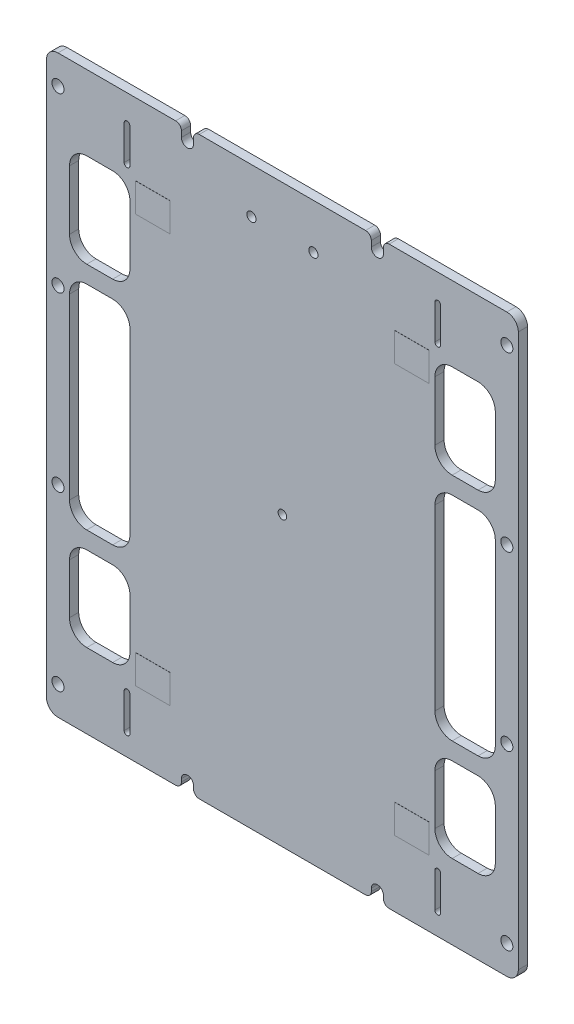
SolidWorks part; units mm, degrees
material "FR4_stuffedProtoboard"
ref_plane "Front Plane" through (0, 0, 0) normal (0, 0, 1) x (1, 0, 0)
ref_plane "Top Plane" through (0, 0, 0) normal (0, 1, 0) x (1, 0, 0)
ref_plane "Right Plane" through (0, 0, 0) normal (1, 0, 0) x (0, 0, -1)
sketch "Sketch1" plane through (0, 0, 0) normal (0, 0, 1) x (1, 0, 0)
  line L1 (-39, -50) -> (39, -50)
  line L2 (-41, -48) -> (-41, 48)
  line L3 (-39, 50) -> (39, 50)
  line L4 (41, -48) -> (41, 48)
  line L5 (-41, -50) -> (41, 50) construction
  line L6 (-41, 50) -> (41, -50) construction
  arc A0 (-39, -50) -> (-41, -48) centre (-39, -48) cw
  arc A1 (39, -50) -> (41, -48) centre (39, -48) ccw
  arc A2 (39, 50) -> (41, 48) centre (39, 48) cw
  arc A3 (-41, 48) -> (-39, 50) centre (-39, 48) cw
  point P0 (0, 0)
  dimension "D3" = 2
  dimension "D1" = 100
  dimension "D2" = 82
extrude "boardOutline" add sketch "Sketch1" along normal blind 1.6
sketch "Sketch2" plane through (0, 0, 1.6) normal (0, 0, 1) x (1, 0, 0)
  line L0 (39, 50) -> (-39, 50) construction
  line L1 (-41, 48) -> (-41, -48) construction
  line L3 (-37.5, 44.2) -> (-37.5, 4.2) construction
  circle A0 centre (0, 0) radius 0.75
  circle A1 centre (-37.5, 44.2) radius 1.05 construction
  circle A2 centre (37.5, 44.2) radius 1.05 construction
  circle A3 centre (37.5, 4.2) radius 1.05 construction
  circle A4 centre (37.5, -35.8) radius 1.05 construction
  circle A5 centre (-37.5, 4.2) radius 1.05 construction
  circle A6 centre (-37.5, -35.8) radius 1.05 construction
  circle A7 centre (-5.38, 42.15) radius 0.8
  circle A8 centre (5.39, 42.15) radius 0.8
  dimension "D1" = 1.5
  dimension "D2" = 2.1
  dimension "D9" = 10.77
  dimension "D7" = 1.6
  dimension "D11" = 7.85
  dimension "D12" = 35.62
  dimension "D3" = 5.8
  dimension "D4" = 3.5
  dimension "D8" = 40
  dimension "D10" = 37.5
  dimension "D5" = 2
  dimension "D6" = 3
extrude "componentHoles" cut sketch "Sketch2" against normal through all
sketch "Sketch4" plane through (0, 0, 1.6) normal (0, 0, 1) x (1, 0, 0)
  line L0 (-27, 39.25) -> (-27, 45.25) construction
  line L1 (-27.5, 39.25) -> (-27.5, 45.25)
  line L2 (-26.5, 39.25) -> (-26.5, 45.25)
  line L3 (39, 50) -> (-39, 50) construction
  line L4 (-41, 48) -> (-41, -48) construction
  line L5 (27, 39.25) -> (27, 45.25) construction
  line L6 (26.5, 39.25) -> (26.5, 45.25)
  line L7 (27.5, 39.25) -> (27.5, 45.25)
  line L8 (27, -46.25) -> (27, -40.25) construction
  line L9 (26.5, -46.25) -> (26.5, -40.25)
  line L10 (27.5, -46.25) -> (27.5, -40.25)
  line L11 (-27, -46.25) -> (-27, -40.25) construction
  line L12 (-27.5, -46.25) -> (-27.5, -40.25)
  line L13 (-26.5, -46.25) -> (-26.5, -40.25)
  line L14 (-27, 39.25) -> (27, 39.25) construction
  arc A0 (-27.5, 39.25) -> (-26.5, 39.25) centre (-27, 39.25) ccw
  arc A1 (-26.5, 45.25) -> (-27.5, 45.25) centre (-27, 45.25) ccw
  arc A2 (26.5, 39.25) -> (27.5, 39.25) centre (27, 39.25) ccw
  arc A3 (27.5, 45.25) -> (26.5, 45.25) centre (27, 45.25) ccw
  arc A4 (26.5, -46.25) -> (27.5, -46.25) centre (27, -46.25) ccw
  arc A5 (27.5, -40.25) -> (26.5, -40.25) centre (27, -40.25) ccw
  arc A6 (-27.5, -46.25) -> (-26.5, -46.25) centre (-27, -46.25) ccw
  arc A7 (-26.5, -40.25) -> (-27.5, -40.25) centre (-27, -40.25) ccw
  point P2 (-27, 42.25)
  point P11 (0, 0)
  point P16 (27, 42.25)
  point P23 (27, -43.25)
  point P30 (-27, -43.25)
  dimension "D1" = 4.75
  dimension "D2" = 13.5
  dimension "D3" = 1
  dimension "D4" = 6
  dimension "D7" = 54
  dimension "D8" = 14
  dimension "D9" = 79.5
  dimension "D5" = 2
  dimension "D6" = 2
extrude "solarCellContactHoles" cut sketch "Sketch4" against normal blind 1.6
sketch "Sketch3" plane through (0, 0, 1.6) normal (0, 0, 1) x (1, 0, 0)
  line L1 (-34, 37) -> (-29.5, 37)
  line L2 (-37, 34) -> (-37, 23.7)
  line L3 (-34, 20.7) -> (-29.5, 20.7)
  line L4 (-26.5, 34) -> (-26.5, 23.7)
  line L5 (-41, 48) -> (-41, -48) construction
  line L6 (-29.5, -22.3) -> (-34, -22.3)
  line L9 (0, 50) -> (0, -50) construction
  line L10 (39, 50) -> (-39, 50) construction
  line L11 (-39, -50) -> (39, -50) construction
  line L12 (-26.5, -25.3) -> (-26.5, -34)
  line L13 (-29.5, -37) -> (-34, -37)
  line L14 (-37, -25.3) -> (-37, -34)
  line L19 (-29.5, -19.3) -> (-34, -19.3)
  line L25 (-26.5, -16.3) -> (-26.5, 14.7)
  line L26 (-29.5, 17.7) -> (-34, 17.7)
  line L27 (-37, -16.3) -> (-37, 14.7)
  arc A0 (-37, 23.7) -> (-34, 20.7) centre (-34, 23.7) ccw
  arc A1 (-29.5, 20.7) -> (-26.5, 23.7) centre (-29.5, 23.7) ccw
  arc A2 (-29.5, 37) -> (-26.5, 34) centre (-29.5, 34) cw
  arc A3 (-34, 37) -> (-37, 34) centre (-34, 34) ccw
  arc A4 (-29.5, -19.3) -> (-26.5, -16.3) centre (-29.5, -16.3) ccw
  arc A5 (-26.5, -34) -> (-29.5, -37) centre (-29.5, -34) cw
  arc A6 (-34, -37) -> (-37, -34) centre (-34, -34) cw
  arc A7 (-34, -22.3) -> (-37, -25.3) centre (-34, -25.3) ccw
  arc A8 (-29.5, -22.3) -> (-26.5, -25.3) centre (-29.5, -25.3) cw
  arc A17 (-34, -19.3) -> (-37, -16.3) centre (-34, -16.3) cw
  arc A18 (-34, 17.7) -> (-37, 14.7) centre (-34, 14.7) ccw
  arc A19 (-26.5, 14.7) -> (-29.5, 17.7) centre (-29.5, 14.7) ccw
  point P12 (-26.5, 20.7)
  point P15 (-26.5, 37)
  point P18 (-37, 37)
  dimension "D5" = 3
  dimension "D10" = 13
  dimension "D7" = 3
  dimension "D11" = 3
  dimension "D1" = 10.5
  dimension "D2" = 29.3
  dimension "D3" = 13
  dimension "D4" = 4
  dimension "D8" = 3
  dimension "D9" = 3
  dimension "D6" = 37
extrude "windows_1side" cut sketch "Sketch3" against normal through all
sketch "Sketch5" plane through (0, 0, 1.6) normal (0, 0, 1) x (1, 0, 0)
  line L0 (-41, 48) -> (-41, -48) construction
  line L1 (-25.5, 37.5) -> (-19.5, 37.5)
  line L2 (-25.5, 37.5) -> (-25.5, 32.5)
  line L3 (-25.5, 32.5) -> (-19.5, 32.5)
  line L4 (-19.5, 37.5) -> (-19.5, 32.5)
  line L6 (19.5, 37.5) -> (19.5, 32.5)
  line L7 (25.5, 37.5) -> (25.5, 32.5)
  line L8 (19.5, 32.5) -> (25.5, 32.5)
  line L9 (19.5, 37.5) -> (25.5, 37.5)
  line L10 (19.5, -33.5) -> (19.5, -38.5)
  line L11 (25.5, -33.5) -> (25.5, -38.5)
  line L12 (19.5, -38.5) -> (25.5, -38.5)
  line L13 (19.5, -33.5) -> (25.5, -33.5)
  line L14 (-25.5, -33.5) -> (-25.5, -38.5)
  line L15 (-19.5, -33.5) -> (-19.5, -38.5)
  line L16 (-25.5, -38.5) -> (-19.5, -38.5)
  line L17 (-25.5, -33.5) -> (-19.5, -33.5)
  line L18 (-25.5, 37.5) -> (19.5, 37.5) construction
  line L19 (-25.5, 37.5) -> (-25.5, -33.5) construction
  arc A0 (-27.5, 39.25) -> (-26.5, 39.25) centre (-27, 39.25) ccw construction
  dimension "D1" = 5
  dimension "D2" = 6
  dimension "D3" = 15.5
  dimension "D4" = 1.75
  dimension "D7" = 45
  dimension "D8" = 71
  dimension "D5" = 2
  dimension "D6" = 2
extrude "contactPads" add sketch "Sketch5" along normal blind 0.02
hole_wizard "M2 Clearance Hole1" positions "Sketch6" profile "Sketch7" hole size "M2" standard "ANSI Metric" end condition through all
sketch "Sketch6" plane through (0, 0, 0) normal (0, 0, -1) x (-1, 0, 0)
  line L5 (39, -50) -> (39, -45) construction
  line L6 (39, -50) -> (-39, -50) construction
  line L7 (39, -45) -> (39, -15) construction
  line L8 (39, -15) -> (39, 15) construction
  line L9 (39, 15) -> (39, 45) construction
  line L10 (39, 45) -> (39, 50) construction
  line L11 (-39, 50) -> (39, 50) construction
  line L15 (37, -27.0602) -> (41, -27.0602) construction
  line L16 (37, -25.3) -> (37, -34) construction
  line L17 (41, 48) -> (41, -48) construction
  point P0 (39, 45)
  point P27 (39, -15)
  point P36 (39, -45)
  point P38 (39, 15)
  point P73 (39, -27.0602)
  dimension "D2" = 5
sketch "Sketch7" plane through (-39, 45, 0) normal (1, 0, 0) x (0, 1, 0)
  line L0 (0, 0) -> (0, 1.62)
  line L1 (0, 1.62) -> (1.05, 1.62)
  line L2 (1.05, 1.62) -> (1.05, 0)
  line L5 (1.05, 0) -> (0, 0)
  line L11 (0, -6.35) -> (0, 107.95) construction
  dimension "Thru Hole Dia." = 2.1
  dimension "Thru Hole Depth" = 1.62
sketch "Sketch10" plane through (0, 0, 0) normal (0, 0, -1) x (-1, 0, 0)
  line L0 (16.5, 48) -> (16.5, 55.0732) construction
  line L1 (15.45, 48) -> (15.45, 55.0732)
  line L2 (17.55, 48) -> (17.55, 55.0732)
  line L3 (16.5, -48.5) -> (16.5, -55.5732) construction
  line L4 (17.55, -48.5) -> (17.55, -55.5732)
  line L5 (15.45, -48.5) -> (15.45, -55.5732)
  line L6 (41, 48) -> (41, -48) construction
  line L8 (39, -50) -> (-39, -50) construction
  line L9 (-39, 50) -> (39, 50) construction
  arc A0 (15.45, 48) -> (17.55, 48) centre (16.5, 48) ccw
  arc A1 (17.55, 55.0732) -> (15.45, 55.0732) centre (16.5, 55.0732) ccw
  arc A2 (17.55, -48.5) -> (15.45, -48.5) centre (16.5, -48.5) ccw
  arc A3 (15.45, -55.5732) -> (17.55, -55.5732) centre (16.5, -55.5732) ccw
  point P2 (16.5, 51.5366)
  point P7 (16.5, -52.0366)
  dimension "D1" = 1.05
  dimension "D2" = 24.5
  dimension "D3" = 2
  dimension "D4" = 1.5
extrude "Cut-Extrude1" cut sketch "Sketch10" against normal through all both and the other way through all
fillet "Fillet3" radius 1 4 edges at (-17.55, 50, 0.8) (-15.45, 50, 0.8) (-15.45, -50, 0.8) (-17.55, -50, 0.8)
mirror "Mirror1" about plane through (0, 0, 0) normal (1, 0, 0) of "Cut-Extrude1", "Fillet3", "windows_1side", "M2 Clearance Hole1"
sketch "thermalContact" plane through (0, 0, 1.6) normal (0, 0, 1) x (1, 0, 0)
  line L0 (-37, 43) -> (-37, 23.7) construction
  line L1 (-34, 20.7) -> (-21, 20.7) construction
  line L2 (-18, 23.7) -> (-18, 43) construction
  line L3 (-21, 46) -> (-34, 46) construction
  line L4 (-41, 48) -> (-41, -162)
  line L5 (39, 50) -> (-39, 50)
  line L6 (41, -162) -> (41, 48)
  line L7 (-39, -164) -> (39, -164)
  line L8 (-41, 48) -> (-41, -162)
  line L9 (39, 50) -> (-39, 50)
  line L10 (41, -162) -> (41, 48)
  line L11 (-39, -164) -> (39, -164)
  line L12 (-37, 43) -> (-37, 23.7)
  line L13 (-34, 20.7) -> (-21, 20.7)
  line L14 (-18, 23.7) -> (-18, 43)
  line L15 (-21, 46) -> (-34, 46)
  line L16 (18, 43) -> (18, 23.7) construction
  line L17 (21, 20.7) -> (34, 20.7) construction
  line L18 (37, 23.7) -> (37, 43) construction
  line L19 (34, 46) -> (21, 46) construction
  line L20 (18, 43) -> (18, 23.7)
  line L21 (21, 20.7) -> (34, 20.7)
  line L22 (37, 23.7) -> (37, 43)
  line L23 (34, 46) -> (21, 46)
  line L24 (-12, -47) -> (12, -47) construction
  line L25 (15, -44) -> (15, -25.3) construction
  line L26 (12, -22.3) -> (-12, -22.3) construction
  line L27 (-15, -25.3) -> (-15, -44) construction
  line L28 (-12, -47) -> (12, -47)
  line L29 (15, -44) -> (15, -25.3)
  line L30 (12, -22.3) -> (-12, -22.3)
  line L31 (-15, -25.3) -> (-15, -44)
  line L32 (-37, -25.3) -> (-37, -44) construction
  line L33 (-34, -47) -> (-21, -47) construction
  line L34 (-18, -44) -> (-18, -25.3) construction
  line L35 (-21, -22.3) -> (-34, -22.3) construction
  line L36 (-37, -25.3) -> (-37, -44)
  line L37 (-34, -47) -> (-21, -47)
  line L38 (-18, -44) -> (-18, -25.3)
  line L39 (-21, -22.3) -> (-34, -22.3)
  line L40 (18, -25.3) -> (18, -44) construction
  line L41 (21, -47) -> (34, -47) construction
  line L42 (37, -44) -> (37, -25.3) construction
  line L43 (34, -22.3) -> (21, -22.3) construction
  line L44 (18, -25.3) -> (18, -44)
  line L45 (21, -47) -> (34, -47)
  line L46 (37, -44) -> (37, -25.3)
  line L47 (34, -22.3) -> (21, -22.3)
  line L48 (-12, -19.3) -> (12, -19.3) construction
  line L49 (15, -16.3) -> (15, 14.7) construction
  line L50 (12, 17.7) -> (-12, 17.7) construction
  line L51 (-15, 14.7) -> (-15, -16.3) construction
  line L52 (-12, -19.3) -> (12, -19.3)
  line L53 (15, -16.3) -> (15, 14.7)
  line L54 (12, 17.7) -> (-12, 17.7)
  line L55 (-15, 14.7) -> (-15, -16.3)
  line L56 (-21, 17.7) -> (-34, 17.7) construction
  line L57 (-37, 14.7) -> (-37, -16.3) construction
  line L58 (-34, -19.3) -> (-21, -19.3) construction
  line L59 (-18, -16.3) -> (-18, 14.7) construction
  line L60 (-21, 17.7) -> (-34, 17.7)
  line L61 (-37, 14.7) -> (-37, -16.3)
  line L62 (-34, -19.3) -> (-21, -19.3)
  line L63 (-18, -16.3) -> (-18, 14.7)
  line L64 (21, -19.3) -> (34, -19.3) construction
  line L65 (37, -16.3) -> (37, 14.7) construction
  line L66 (34, 17.7) -> (21, 17.7) construction
  line L67 (18, 14.7) -> (18, -16.3) construction
  line L68 (21, -19.3) -> (34, -19.3)
  line L69 (37, -16.3) -> (37, 14.7)
  line L70 (34, 17.7) -> (21, 17.7)
  line L71 (18, 14.7) -> (18, -16.3)
  line L72 (-12, 20.7) -> (12, 20.7) construction
  line L73 (15, 23.7) -> (15, 43) construction
  line L74 (12, 46) -> (-12, 46) construction
  line L75 (-15, 43) -> (-15, 23.7) construction
  line L76 (-12, 20.7) -> (12, 20.7)
  line L77 (15, 23.7) -> (15, 43)
  line L78 (12, 46) -> (-12, 46)
  line L79 (-15, 43) -> (-15, 23.7)
  line L80 (-21, -50) -> (-34, -50) construction
  line L81 (-37, -53) -> (-37, -61) construction
  line L82 (-34, -64) -> (-21, -64) construction
  line L83 (-18, -61) -> (-18, -53) construction
  line L84 (-21, -50) -> (-34, -50)
  line L85 (-37, -53) -> (-37, -61)
  line L86 (-34, -64) -> (-21, -64)
  line L87 (-18, -61) -> (-18, -53)
  line L88 (-15, -53) -> (-15, -61) construction
  line L89 (-12, -64) -> (12, -64) construction
  line L90 (15, -61) -> (15, -53) construction
  line L91 (12, -50) -> (-12, -50) construction
  line L92 (-15, -53) -> (-15, -61)
  line L93 (-12, -64) -> (12, -64)
  line L94 (15, -61) -> (15, -53)
  line L95 (12, -50) -> (-12, -50)
  line L96 (18, -53) -> (18, -61) construction
  line L97 (21, -64) -> (34, -64) construction
  line L98 (37, -61) -> (37, -53) construction
  line L99 (34, -50) -> (21, -50) construction
  line L100 (18, -53) -> (18, -61)
  line L101 (21, -64) -> (34, -64)
  line L102 (37, -61) -> (37, -53)
  line L103 (34, -50) -> (21, -50)
  arc A0 (-34, 46) -> (-37, 43) centre (-34, 43) ccw construction
  arc A1 (-37, 23.7) -> (-34, 20.7) centre (-34, 23.7) ccw construction
  arc A2 (-21, 20.7) -> (-18, 23.7) centre (-21, 23.7) ccw construction
  arc A3 (-18, 43) -> (-21, 46) centre (-21, 43) ccw construction
  arc A4 (-39, 50) -> (-41, 48) centre (-39, 48) ccw
  arc A5 (41, 48) -> (39, 50) centre (39, 48) ccw
  arc A6 (39, -164) -> (41, -162) centre (39, -162) ccw
  arc A7 (-41, -162) -> (-39, -164) centre (-39, -162) ccw
  arc A8 (-39, 50) -> (-41, 48) centre (-39, 48) ccw
  arc A9 (41, 48) -> (39, 50) centre (39, 48) ccw
  arc A10 (39, -164) -> (41, -162) centre (39, -162) ccw
  arc A11 (-41, -162) -> (-39, -164) centre (-39, -162) ccw
  arc A12 (-34, 46) -> (-37, 43) centre (-34, 43) ccw
  arc A13 (-37, 23.7) -> (-34, 20.7) centre (-34, 23.7) ccw
  arc A14 (-21, 20.7) -> (-18, 23.7) centre (-21, 23.7) ccw
  arc A15 (-18, 43) -> (-21, 46) centre (-21, 43) ccw
  arc A16 (21, 46) -> (18, 43) centre (21, 43) ccw construction
  arc A17 (18, 23.7) -> (21, 20.7) centre (21, 23.7) ccw construction
  arc A18 (34, 20.7) -> (37, 23.7) centre (34, 23.7) ccw construction
  arc A19 (37, 43) -> (34, 46) centre (34, 43) ccw construction
  arc A20 (21, 46) -> (18, 43) centre (21, 43) ccw
  arc A21 (18, 23.7) -> (21, 20.7) centre (21, 23.7) ccw
  arc A22 (34, 20.7) -> (37, 23.7) centre (34, 23.7) ccw
  arc A23 (37, 43) -> (34, 46) centre (34, 43) ccw
  arc A24 (-15, -44) -> (-12, -47) centre (-12, -44) ccw construction
  arc A25 (12, -47) -> (15, -44) centre (12, -44) ccw construction
  arc A26 (15, -25.3) -> (12, -22.3) centre (12, -25.3) ccw construction
  arc A27 (-12, -22.3) -> (-15, -25.3) centre (-12, -25.3) ccw construction
  arc A28 (-15, -44) -> (-12, -47) centre (-12, -44) ccw
  arc A29 (12, -47) -> (15, -44) centre (12, -44) ccw
  arc A30 (15, -25.3) -> (12, -22.3) centre (12, -25.3) ccw
  arc A31 (-12, -22.3) -> (-15, -25.3) centre (-12, -25.3) ccw
  arc A32 (-34, -22.3) -> (-37, -25.3) centre (-34, -25.3) ccw construction
  arc A33 (-37, -44) -> (-34, -47) centre (-34, -44) ccw construction
  arc A34 (-21, -47) -> (-18, -44) centre (-21, -44) ccw construction
  arc A35 (-18, -25.3) -> (-21, -22.3) centre (-21, -25.3) ccw construction
  arc A36 (-34, -22.3) -> (-37, -25.3) centre (-34, -25.3) ccw
  arc A37 (-37, -44) -> (-34, -47) centre (-34, -44) ccw
  arc A38 (-21, -47) -> (-18, -44) centre (-21, -44) ccw
  arc A39 (-18, -25.3) -> (-21, -22.3) centre (-21, -25.3) ccw
  arc A40 (21, -22.3) -> (18, -25.3) centre (21, -25.3) ccw construction
  arc A41 (18, -44) -> (21, -47) centre (21, -44) ccw construction
  arc A42 (34, -47) -> (37, -44) centre (34, -44) ccw construction
  arc A43 (37, -25.3) -> (34, -22.3) centre (34, -25.3) ccw construction
  arc A44 (21, -22.3) -> (18, -25.3) centre (21, -25.3) ccw
  arc A45 (18, -44) -> (21, -47) centre (21, -44) ccw
  arc A46 (34, -47) -> (37, -44) centre (34, -44) ccw
  arc A47 (37, -25.3) -> (34, -22.3) centre (34, -25.3) ccw
  arc A48 (-15, -16.3) -> (-12, -19.3) centre (-12, -16.3) ccw construction
  arc A49 (12, -19.3) -> (15, -16.3) centre (12, -16.3) ccw construction
  arc A50 (15, 14.7) -> (12, 17.7) centre (12, 14.7) ccw construction
  arc A51 (-12, 17.7) -> (-15, 14.7) centre (-12, 14.7) ccw construction
  arc A52 (-15, -16.3) -> (-12, -19.3) centre (-12, -16.3) ccw
  arc A53 (12, -19.3) -> (15, -16.3) centre (12, -16.3) ccw
  arc A54 (15, 14.7) -> (12, 17.7) centre (12, 14.7) ccw
  arc A55 (-12, 17.7) -> (-15, 14.7) centre (-12, 14.7) ccw
  arc A56 (-18, 14.7) -> (-21, 17.7) centre (-21, 14.7) ccw construction
  arc A57 (-34, 17.7) -> (-37, 14.7) centre (-34, 14.7) ccw construction
  arc A58 (-37, -16.3) -> (-34, -19.3) centre (-34, -16.3) ccw construction
  arc A59 (-21, -19.3) -> (-18, -16.3) centre (-21, -16.3) ccw construction
  arc A60 (-18, 14.7) -> (-21, 17.7) centre (-21, 14.7) ccw
  arc A61 (-34, 17.7) -> (-37, 14.7) centre (-34, 14.7) ccw
  arc A62 (-37, -16.3) -> (-34, -19.3) centre (-34, -16.3) ccw
  arc A63 (-21, -19.3) -> (-18, -16.3) centre (-21, -16.3) ccw
  arc A64 (18, -16.3) -> (21, -19.3) centre (21, -16.3) ccw construction
  arc A65 (34, -19.3) -> (37, -16.3) centre (34, -16.3) ccw construction
  arc A66 (37, 14.7) -> (34, 17.7) centre (34, 14.7) ccw construction
  arc A67 (21, 17.7) -> (18, 14.7) centre (21, 14.7) ccw construction
  arc A68 (18, -16.3) -> (21, -19.3) centre (21, -16.3) ccw
  arc A69 (34, -19.3) -> (37, -16.3) centre (34, -16.3) ccw
  arc A70 (37, 14.7) -> (34, 17.7) centre (34, 14.7) ccw
  arc A71 (21, 17.7) -> (18, 14.7) centre (21, 14.7) ccw
  arc A72 (-15, 23.7) -> (-12, 20.7) centre (-12, 23.7) ccw construction
  arc A73 (12, 20.7) -> (15, 23.7) centre (12, 23.7) ccw construction
  arc A74 (15, 43) -> (12, 46) centre (12, 43) ccw construction
  arc A75 (-12, 46) -> (-15, 43) centre (-12, 43) ccw construction
  arc A76 (-15, 23.7) -> (-12, 20.7) centre (-12, 23.7) ccw
  arc A77 (12, 20.7) -> (15, 23.7) centre (12, 23.7) ccw
  arc A78 (15, 43) -> (12, 46) centre (12, 43) ccw
  arc A79 (-12, 46) -> (-15, 43) centre (-12, 43) ccw
  arc A80 (-34, -50) -> (-37, -53) centre (-34, -53) ccw construction
  arc A81 (-37, -61) -> (-34, -64) centre (-34, -61) ccw construction
  arc A82 (-21, -64) -> (-18, -61) centre (-21, -61) ccw construction
  arc A83 (-18, -53) -> (-21, -50) centre (-21, -53) ccw construction
  arc A84 (-34, -50) -> (-37, -53) centre (-34, -53) ccw
  arc A85 (-37, -61) -> (-34, -64) centre (-34, -61) ccw
  arc A86 (-21, -64) -> (-18, -61) centre (-21, -61) ccw
  arc A87 (-18, -53) -> (-21, -50) centre (-21, -53) ccw
  arc A88 (-15, -61) -> (-12, -64) centre (-12, -61) ccw construction
  arc A89 (12, -64) -> (15, -61) centre (12, -61) ccw construction
  arc A90 (15, -53) -> (12, -50) centre (12, -53) ccw construction
  arc A91 (-12, -50) -> (-15, -53) centre (-12, -53) ccw construction
  arc A92 (-15, -61) -> (-12, -64) centre (-12, -61) ccw
  arc A93 (12, -64) -> (15, -61) centre (12, -61) ccw
  arc A94 (15, -53) -> (12, -50) centre (12, -53) ccw
  arc A95 (-12, -50) -> (-15, -53) centre (-12, -53) ccw
  arc A96 (21, -50) -> (18, -53) centre (21, -53) ccw construction
  arc A97 (18, -61) -> (21, -64) centre (21, -61) ccw construction
  arc A98 (34, -64) -> (37, -61) centre (34, -61) ccw construction
  arc A99 (37, -53) -> (34, -50) centre (34, -53) ccw construction
  arc A100 (18, -61) -> (21, -64) centre (21, -61) ccw
  arc A101 (34, -64) -> (37, -61) centre (34, -61) ccw
  arc A102 (37, -53) -> (34, -50) centre (34, -53) ccw
  arc A103 (21, -50) -> (18, -53) centre (21, -53) ccw
  dimension "D1" = 0
